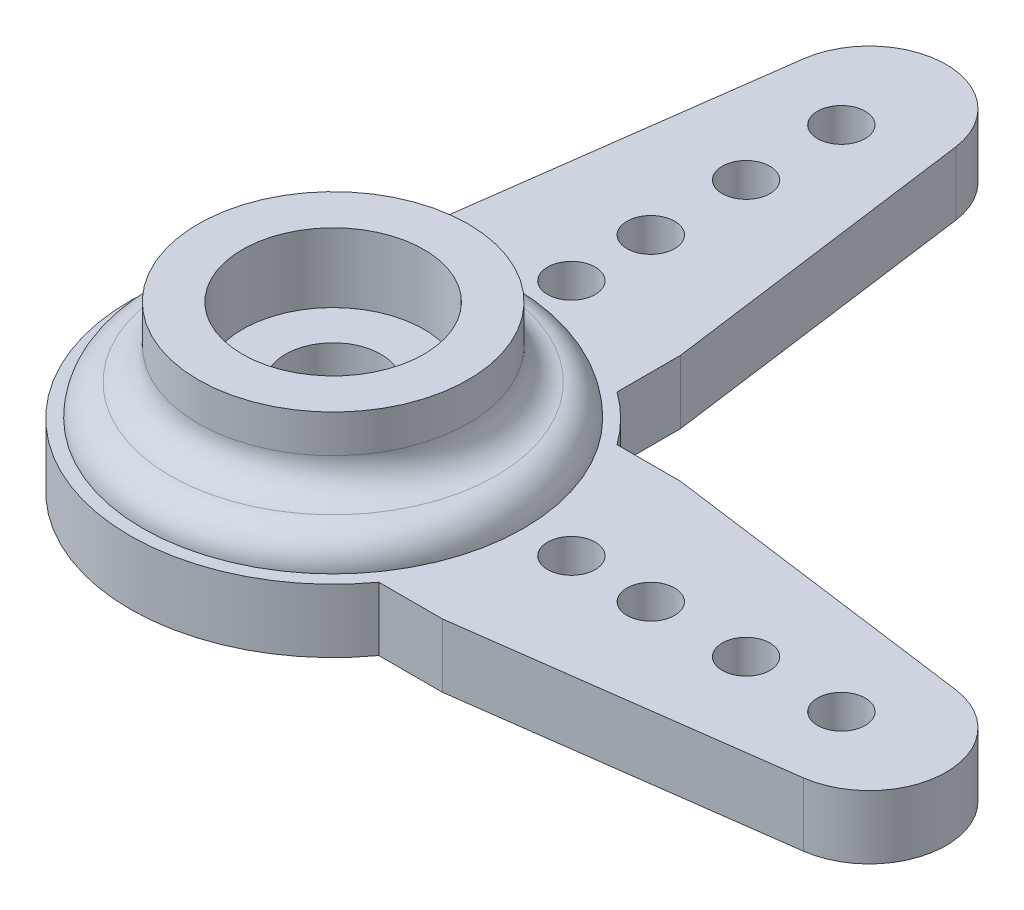
SolidWorks part; units mm, degrees
material "ABS"
ref_plane "Front Plane" through (0, 0, 0) normal (0, 0, 1) x (1, 0, 0)
ref_plane "Top Plane" through (0, 0, 0) normal (0, 1, 0) x (1, 0, 0)
ref_plane "Right Plane" through (0, 0, 0) normal (1, 0, 0) x (0, 0, -1)
sketch "Sketch1" plane through (0, 0, 0) normal (0, 1, 0) x (1, 0, 0)
  line L0 (0, -1000) -> (0, 49000) construction
  line L1 (-3.75, 5.1863) -> (-3.75, 7.1863)
  line L2 (-3.75, 7.1863) -> (-2.4, 17.2018)
  line L3 (3.75, 7.1863) -> (2.4, 17.2018)
  line L4 (3.75, 5.1863) -> (3.75, 7.1863)
  line L5 (7.1863, 3.75) -> (17.2018, 2.4)
  line L6 (5.1863, 3.75) -> (7.1863, 3.75)
  line L7 (5.1863, -3.75) -> (7.1863, -3.75)
  line L8 (7.1863, -3.75) -> (17.2018, -2.4)
  arc A0 (-3.75, 5.1863) -> (5.1863, -3.75) centre (0, 0) ccw
  circle A1 centre (0, 0) radius 1.5
  arc A2 (-2.4, 17.2018) -> (2.4, 17.2018) centre (0, 16.8783) cw
  circle A3 centre (0, 16) radius 0.75
  circle A4 centre (0, 13) radius 0.75
  circle A5 centre (0, 10) radius 0.75
  circle A6 centre (0, 7.5) radius 0.75
  circle A7 centre (7.5, 0) radius 0.75
  circle A8 centre (10, 0) radius 0.75
  circle A9 centre (13, 0) radius 0.75
  circle A10 centre (16, 0) radius 0.75
  arc A11 (17.2018, 2.4) -> (17.2018, -2.4) centre (16.8783, 0) cw
  arc A12 (5.1863, 3.75) -> (3.75, 5.1863) centre (0, 0) ccw
  point P10 (0, 19.3)
  dimension "D1" = 3
  dimension "D2" = 12.8
  dimension "D4" = 2
  dimension "D5" = 2.4
  dimension "D7" = 1.5
  dimension "D10" = 2.5
  dimension "D11" = 16
  dimension "D3" = 19.3
  dimension "D6" = 3.75
  dimension "D8" = 3
  dimension "D9" = 3
  dimension "D13" = 90
  dimension "D12" = 2
extrude "Boss-Extrude1" add sketch "Sketch1" along normal blind 2
sketch "Sketch4" plane through (0, 2, 0) normal (0, 1, 0) x (1, 0, 0)
  circle A0 centre (0, 0) radius 2.8575
  circle A1 centre (0, 0) radius 4.25
  dimension "D1" = 5.715
  dimension "D2" = 8.5
extrude "Boss-Extrude2" add sketch "Sketch4" along normal blind 3.175
sketch "Sketch5" plane through (0, 2, 0) normal (0, 1, 0) x (1, 0, 0)
  circle A0 centre (0, 0) radius 6
  dimension "D1" = 12
extrude "Boss-Extrude3" add sketch "Sketch5" along normal blind 1
fillet "Fillet1" radius 1 1 edges at (0, 3, 6)
fillet "Fillet2" radius 1 1 edges at (0, 3, 4.25)
sketch "Sketch7" plane through (0, 0, 0) normal (0, -1, 0) x (1, 0, 0)
  circle A0 centre (0, 0) radius 1.5
  dimension "D1" = 3
extrude "Cut-Extrude1" cut sketch "Sketch7" against normal through all
